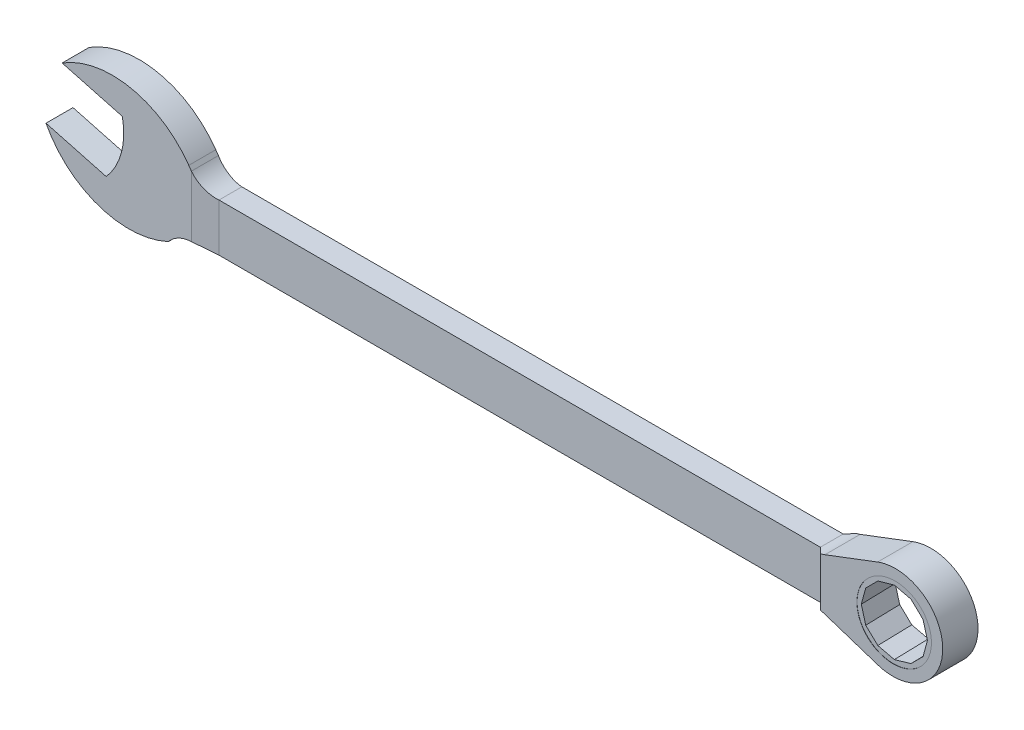
SolidWorks part; units mm, degrees
material "V2a"
ref_plane "Vorne" through (0, 0, 0) normal (0, 0, 1) x (1, 0, 0)
ref_plane "Oben" through (0, 0, 0) normal (0, 1, 0) x (1, 0, 0)
ref_plane "Rechts" through (0, 0, 0) normal (1, 0, 0) x (0, 0, -1)
sketch "Skizze1" plane through (0, 0, 0) normal (0, 0, 1) x (1, 0, 0)
  line L0 (-66.2747, 0) -> (185, 0) construction
  line L1 (-216.7189, 31.8695) -> (-187.7412, 24.105)
  line L2 (-224.4835, 2.8918) -> (-216.7189, 31.8695) construction
  line L3 (-195.5057, -4.8728) -> (-224.4835, 2.8918)
  line L4 (-165.5815, -17.0534) -> (-161.4715, -11.5)
  line L6 (-161.4715, -11.5) -> (150, -11.5)
  line L8 (-155.7358, 19.6915) -> (-150, 11.5)
  line L9 (-150, 11.5) -> (150, 11.5)
  line L10 (150, 11.5) -> (177.2097, 21.4035)
  line L11 (150, -11.5) -> (177.2097, -21.4035)
  line L12 (-311.4715, 41.7293) -> (0, -41.7293) construction
  line L13 (-155.7358, 23.4553) -> (-155.7358, 1.9426) construction
  line L14 (185, 24.4912) -> (185, -7.8287) construction
  line L15 (185, 0) -> (200, 0) construction
  line L16 (200, 0) -> (215, 0) construction
  line L17 (0, 0) -> (0, 13.3975) construction
  line L18 (-150, 11.5) -> (-155.7358, 11.5) construction
  line L19 (-161.4715, -11.5) -> (-155.7358, -11.5) construction
  arc A0 (177.2097, -21.4035) -> (177.2097, 21.4035) centre (185, 0) ccw
  arc A1 (-216.7189, 31.8695) -> (-155.7358, 19.6915) centre (-192.5976, -6.1194) cw
  arc A2 (-224.4835, 2.8918) -> (-165.5815, -17.0534) centre (-184.5993, 23.7305) ccw
  circle A3 centre (185, 0) radius 15 construction
  arc A4 (-195.5057, -4.8728) -> (-187.7412, 24.105) centre (-220.6012, 17.3807) ccw
  point P24 (-155.7358, 0)
  dimension "D1" = 30
  dimension "D7" = 45
  dimension "D4" = 23
  dimension "D5" = 15
  dimension "D8" = 10
  dimension "D3" = 55
  dimension "D9" = 300
  dimension "D10" = 40
  dimension "D11" = 35
  dimension "D12" = 150
  dimension "D6" = 30
extrude "Aufsatz-Linear austragen2" add sketch "Skizze1" along normal blind 20 contours L6 L11 A0 L10 L9 L8 A1 L1 L3 | L10 A0 L11 region at (-7.0508, 1.4328, 0)
fillet "Verrundung1" radius 15 3 edges at (150, 11.5, 10) (150, -11.5, 10) (-150, 11.5, 10)
sketch "Skizze5" plane through (0, 0, 0) normal (0, 1, 0) x (1, 0, 0)
  line L0 (147.3551, -15.5) -> (150.3551, -18.5)
  line L1 (-224.4835, -20) -> (-224.4835, 0) construction
  line L3 (207.7772, -17) -> (207.7772, 0)
  line L4 (147.3551, 0) -> (147.3551, -20) construction
  line L5 (147.3551, -15.5) -> (-142.1915, -15.5)
  line L6 (207.7772, 0) -> (177.2097, 0) construction
  line L7 (150.3551, -18.5) -> (207.7772, -17)
  line L8 (147.3551, -4.5) -> (150.3551, -1.5)
  line L9 (-142.1915, 0) -> (-142.1915, -20) construction
  line L10 (150.3551, -1.5) -> (207.7772, 0)
  line L11 (147.3551, -4.5) -> (-142.1915, -4.5)
  line L12 (-142.1915, -15.5) -> (-154.4788, -16.5)
  line L13 (-154.4788, -20) -> (-154.4788, 0) construction
  line L14 (-142.1915, -4.5) -> (-154.4788, -3.5)
  line L15 (-154.4788, -16.5) -> (-224.4835, -16.5)
  line L17 (-224.4835, -16.5) -> (-224.4835, -3.5)
  line L18 (-224.4835, -3.5) -> (-154.4788, -3.5)
  line L19 (-84.1609, -10) -> (83.8548, -10) construction
  line L20 (-161.4715, -20) -> (147.3551, -20) construction
  line L21 (-161.4715, 0) -> (147.3551, 0) construction
  point P20 (207.7772, 0)
  dimension "D1" = 13
  dimension "D2" = 11
  dimension "D3" = 90
  dimension "D4" = 3
extrude "Schnitt-Linear austragen3" cut sketch "Skizze5" against normal through all and the other way through all flip side to cut
sketch "Skizze8" plane through (-1.2786, 0, 22.461) normal (0.0261, 0, 0.9997) x (0.9997, 0, -0.0261)
  line L0 (201.8713, 0) -> (186.3421, 0) construction
  line L1 (201.8713, 0) -> (199.7908, 7.7646)
  line L2 (199.7908, 7.7646) -> (194.1067, 13.4486)
  line L3 (194.1067, 13.4486) -> (186.3421, 15.5291)
  line L4 (186.3421, 15.5291) -> (178.5776, 13.4486)
  line L5 (178.5776, 13.4486) -> (172.8935, 7.7646)
  line L6 (172.8935, 7.7646) -> (170.813, 0)
  line L7 (170.813, 0) -> (172.8935, -7.7646)
  line L8 (172.8935, -7.7646) -> (178.5776, -13.4486)
  line L9 (178.5776, -13.4486) -> (186.3421, -15.5291)
  line L10 (186.3421, -15.5291) -> (194.1067, -13.4486)
  line L11 (194.1067, -13.4486) -> (199.7908, -7.7646)
  line L12 (199.7908, -7.7646) -> (201.8713, 0)
  circle A0 centre (186.3421, 0) radius 15 construction
  ellipse E0 centre (186.3421, 0) end of major axis (209.1271, 0) minor radius 22.7772 (178.5492, -21.4035) -> (178.5492, 21.4035) ccw construction
  dimension "D1" = 30
extrude "Schnitt-Linear austragen6" cut sketch "Skizze8" against normal through all
sketch "Skizze7" plane through (-0.374, 0, 5.4374) normal (-0.0261, 0, -0.9997) x (-0.9997, 0, 0.0261)
  circle A0 centre (-184.9933, 0) radius 17.5
  circle A1 centre (-184.9933, 0) radius 15.5291 construction
  dimension "D1" = 35
extrude "Schnitt-Linear austragen5" cut sketch "Skizze7" against normal blind 0.1
sketch "Skizze9" plane through (0.5855, 0, 22.4123) normal (0.0261, 0, 0.9997) x (0.9997, 0, -0.0261)
  circle A0 centre (184.4774, 0) radius 17.5
  circle A1 centre (184.4774, 0) radius 17.5 construction
extrude "Schnitt-Linear austragen7" cut sketch "Skizze9" against normal blind 0.1
fillet "Verrundung5" radius 15 1 edges at (-161.4715, -11.5, 10)
equation "\"D1@Skizze1\"=\"D2@Skizze1\""
equation "\"D12@Skizze1\"=\"D9@Skizze1\"/2"
equation "\"D6@Skizze1\"=\"D2@Skizze1\""
equation "\"D8@Skizze1\"=\"D2@Skizze1\"/3"
equation "\"D1@Skizze7\"=\"D2@Skizze1\"+5"
equation "\"D2@Skizze5\"=\"D1@Skizze5\"-2"
equation "\"D1@Skizze8\"=\"D2@Skizze1\""
